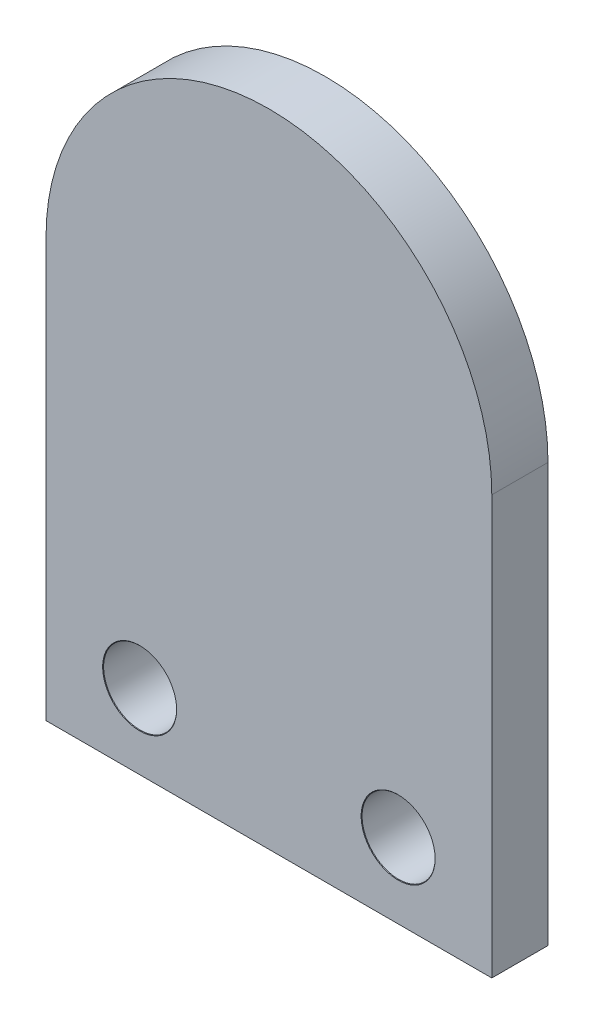
SolidWorks part; units mm, degrees
ref_plane "Front Plane" through (0, 0, 0) normal (0, 0, 1) x (1, 0, 0)
ref_plane "Top Plane" through (0, 0, 0) normal (0, 1, 0) x (1, 0, 0)
ref_plane "Right Plane" through (0, 0, 0) normal (1, 0, 0) x (0, 0, -1)
sketch "Sketch1" plane through (0, 0, 0) normal (0, 0, 1) x (1, 0, 0)
  line L0 (-11.9, 0) -> (-11.9, -22.34)
  line L1 (-11.9, -22.34) -> (11.9, -22.34)
  line L2 (11.9, -22.34) -> (11.9, 0)
  arc A0 (11.9, 0) -> (-11.9, 0) centre (0, 0) ccw
  dimension "D1" = 22.34
  dimension "D2" = 23.8
extrude "Boss-Extrude1" add sketch "Sketch1" along normal blind 3
sketch "Sketch2" plane through (0, 0, 0) normal (0, 0, -1) x (-1, 0, 0)
  circle A0 centre (0, 0) radius 6 construction
  circle A1 centre (0, 6) radius 1.95
  circle A2 centre (6, 0) radius 1.95
  circle A3 centre (0, -6) radius 1.95
  circle A4 centre (-6, 0) radius 1.95
  point P14 (0, 0)
  dimension "D1" = 12
  dimension "D2" = 3.9
  dimension "D3" = 4
extrude "Boss-Extrude2" add sketch "Sketch2" along normal blind 3
hole_wizard "M3.5 Clearance Hole1" positions "Sketch3" profile "Sketch4" hole size "M3.5" standard "ANSI Metric" end condition through all
sketch "Sketch3" plane through (0, 0, 3) normal (0, 0, 1) x (1, 0, 0)
  point P0 (6.9, -18.34)
  point P3 (-6.9, -18.34)
sketch "Sketch4" plane through (6.9, -18.34, 3) normal (1, 0, 0) x (0, -1, 0)
  line L0 (0, 0) -> (0, 6)
  line L1 (0, 6) -> (1.95, 6)
  line L2 (1.95, 6) -> (1.95, 0.025)
  line L3 (1.95, 0.025) -> (1.975, 0)
  line L5 (1.975, 0) -> (0, 0)
  line L6 (-1.95, 0.025) -> (-1.975, 0) construction
  line L11 (0, -6.35) -> (0, 107.95) construction
  dimension "Thru Hole Dia." = 3.9
  dimension "Thru Hole Depth" = 6
  dimension "Near C'Sink Dia." = 3.95
  dimension "Near C'Sink Angle" = 90
